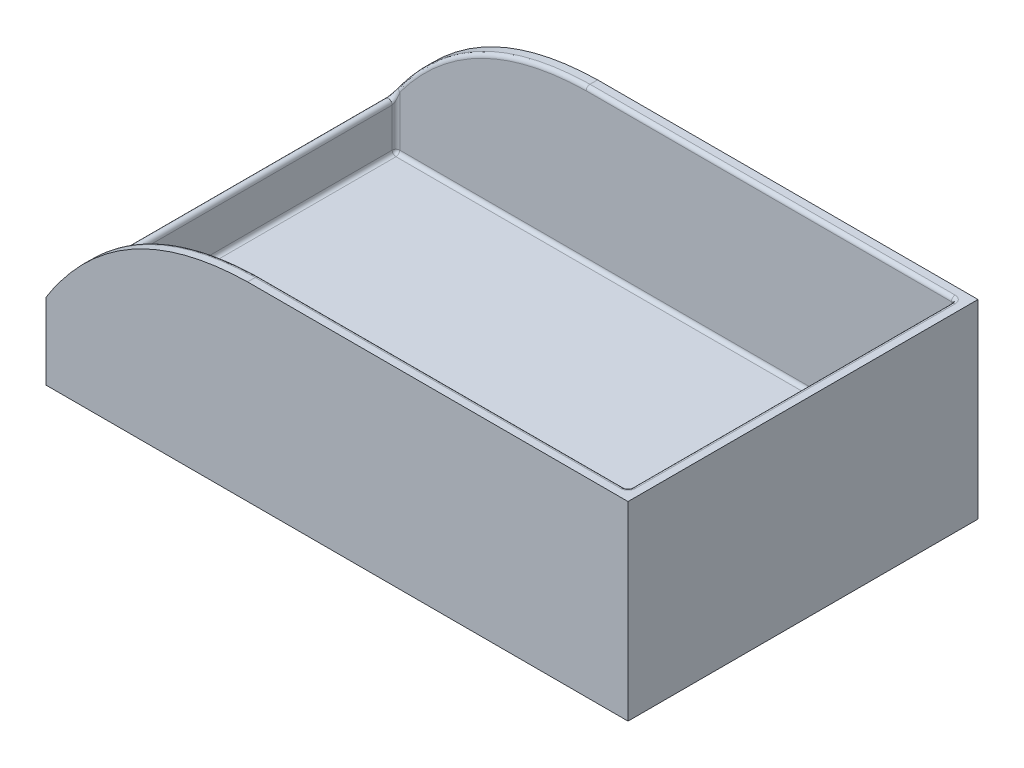
SolidWorks part; units mm, degrees
ref_plane "Front Plane" through (0, 0, 0) normal (0, 0, 1) x (1, 0, 0)
ref_plane "Top Plane" through (0, 0, 0) normal (0, 1, 0) x (1, 0, 0)
ref_plane "Right Plane" through (0, 0, 0) normal (1, 0, 0) x (0, 0, -1)
sketch "Sketch2" plane through (0, 0, 0) normal (0, 0, 1) x (1, 0, 0)
  line L0 (-765, 0) -> (765, 0)
  line L1 (765, 0) -> (765, 500)
  line L2 (765, 500) -> (-235, 500)
  line L3 (-765, 200) -> (-765, 0)
  spline S0 degree 2 poles (-235, 500) (-580.9395, 493.3169) (-765, 200) knots 0 0 0 1 1 1
  point P5 (0, 0)
  dimension "D1" = 1530
  dimension "D2" = 500
  dimension "D3" = 1000
  dimension "D4" = 200
extrude "Boss-Extrude1" add sketch "Sketch2" along normal blind 920
shell "Shell5" thickness 30 removed face at (265, 500, 460) removed face at (-367.5, 425, 460)
sketch "Sketch12" plane through (-765, 0, 0) normal (-1, 0, 0) x (0, 0, 1)
  line L0 (0, 200) -> (0, 0) construction
  line L1 (100, 25) -> (820, 25)
  line L2 (100, 25) -> (100, 75)
  line L3 (100, 75) -> (820, 75)
  line L4 (820, 25) -> (820, 75)
  line L5 (920, 200) -> (920, 0) construction
  line L6 (920, 0) -> (0, 0) construction
  dimension "D1" = 100
  dimension "D2" = 100
  dimension "D3" = 25
  dimension "D4" = 50
extrude "Cut-Extrude3" cut sketch "Sketch12" against normal blind 1430
sketch "Sketch13" plane through (-765, 0, 0) normal (-1, 0, 0) x (0, 0, 1)
  line L0 (87.5, 50) -> (112.5, 50) construction
  line L1 (100, 75) -> (100, 25) construction
  line L2 (87.5, 62.5) -> (112.5, 62.5)
  line L3 (87.5, 37.5) -> (112.5, 37.5)
  line L4 (807.5, 50) -> (832.5, 50) construction
  line L5 (820, 25) -> (820, 75) construction
  line L6 (807.5, 62.5) -> (832.5, 62.5)
  line L7 (807.5, 37.5) -> (832.5, 37.5)
  arc A0 (87.5, 62.5) -> (87.5, 37.5) centre (87.5, 50) ccw
  arc A1 (112.5, 37.5) -> (112.5, 62.5) centre (112.5, 50) ccw
  arc A2 (807.5, 62.5) -> (807.5, 37.5) centre (807.5, 50) ccw
  arc A3 (832.5, 37.5) -> (832.5, 62.5) centre (832.5, 50) ccw
  point P4 (100, 50)
  point P10 (820, 50)
  point P18 (100, 62.5)
  dimension "D1" = 25
  dimension "D2" = 25
  dimension "D3" = 25
  dimension "D4" = 25
extrude "Cut-Extrude4" cut sketch "Sketch13" against normal blind 1430
fillet "Fillet1" radius 10 27 edges at (735, 300, 890) (0, 100, 890) (-735, 172.2144, 890) (-735, 172.2144, 30) (-735, 100, 460) (0, 100, 30) (735, 300, 30) (735, 100, 460) (250, 500, 890) (735, 500, 460) (250, 500, 30) (-450.6783, 462.6232, 30) (-735, 244.4289, 460) (-540.4697, 421.6585, 890) (-765, 31.25, 100) (-765, 37.5, 93.75) (-765, 50, 75) (-765, 62.5, 93.75) (-765, 68.75, 100) (-765, 31.25, 820) (-765, 37.5, 826.25) (-765, 50, 845) (-765, 62.5, 826.25) (-765, 68.75, 820) (-765, 75, 460) (-765, 25, 460) (-765, 200, 460)
